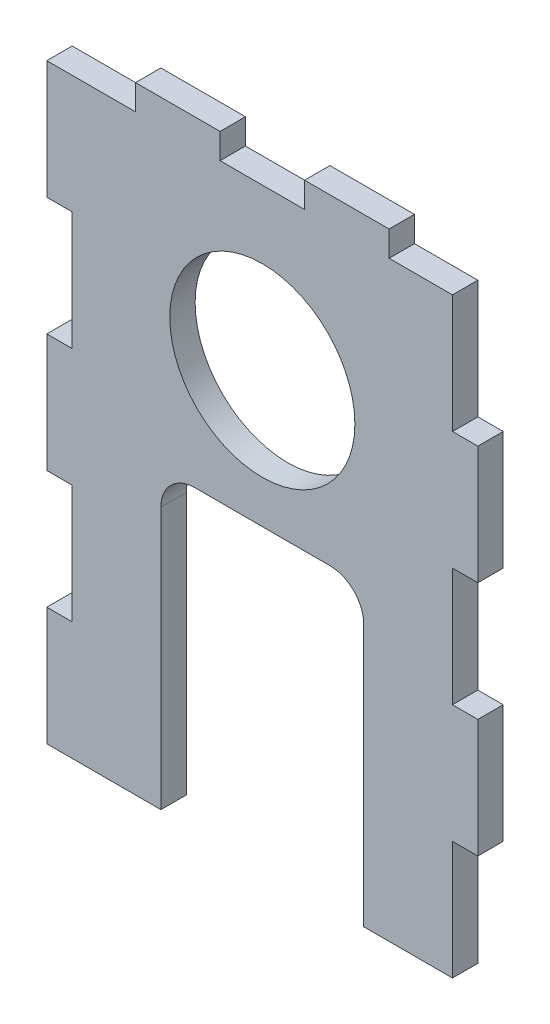
SolidWorks part; units mm, degrees
ref_plane "Front Plane" through (0, 0, 0) normal (0, 0, 1) x (1, 0, 0)
ref_plane "Top Plane" through (0, 0, 0) normal (0, 1, 0) x (1, 0, 0)
ref_plane "Right Plane" through (0, 0, 0) normal (1, 0, 0) x (0, 0, -1)
sketch "Sketch1" plane through (0, 0, 0) normal (0, 0, 1) x (1, 0, 0)
  line L1 (-22.5, -35) -> (22.5, -35)
  line L2 (-22.5, -35) -> (-22.5, 35)
  line L3 (-22.5, 35) -> (22.5, 35)
  line L4 (22.5, -35) -> (22.5, 35)
  line L5 (-22.5, -35) -> (22.5, 35) construction
  line L6 (-22.5, 35) -> (22.5, -35) construction
  point P0 (0, 0)
  dimension "D1" = 70
  dimension "D2" = 45
extrude "Boss-Extrude1" add sketch "Sketch1" along normal blind 3 contours L2 L3 L4 L1
sketch "Sketch2" plane through (0, 0, 3) normal (0, 0, 1) x (1, 0, 0)
  line L0 (-22.5, -35) -> (22.5, -35) construction
  line L1 (-12, 0) -> (12, 0)
  line L2 (-12, 0) -> (-12, -35)
  line L3 (-12, -35) -> (12, -35)
  line L4 (12, 0) -> (12, -35)
  line L5 (-12, 0) -> (12, -35) construction
  line L6 (-12, -35) -> (12, 0) construction
  circle A0 centre (0, 16) radius 10.95
  point P2 (0, -17.5)
  dimension "D1" = 21.9
  dimension "D2" = 16
  dimension "D3" = 24
  dimension "D4" = 35
extrude "Cut-Extrude1" cut sketch "Sketch2" against normal through all
fillet "Fillet1" radius 4 2 edges at (12, 0, 1.5) (-12, 0, 1.5)
sketch "Sketch4" plane through (0, 0, 3) normal (0, 0, 1) x (1, 0, 0)
  line L0 (0, 35) -> (0, 41.52) construction
  line L1 (-15, 35) -> (-5, 35)
  line L2 (-15, 35) -> (-15, 38)
  line L3 (-15, 38) -> (-5, 38)
  line L4 (-5, 35) -> (-5, 38)
  line L5 (-22.5, 35) -> (22.5, 35) construction
  line L6 (5, 35) -> (5, 38)
  line L7 (15, 38) -> (5, 38)
  line L8 (15, 35) -> (15, 38)
  line L9 (15, 35) -> (5, 35)
  dimension "D1" = 3
  dimension "D2" = 10
  dimension "D3" = 10
extrude "Boss-Extrude3" add sketch "Sketch4" against normal up to surface (3 mm away) up to face at (0, -7.6343, 0)
sketch "Sketch3" plane through (0, 0, 0) normal (0, 0, -1) x (-1, 0, 0)
  line L0 (22.5, 7) -> (22.5, -7)
  line L1 (22.5, 35) -> (25.5, 35)
  line L2 (22.5, 35) -> (22.5, 21)
  line L3 (22.5, 21) -> (25.5, 21)
  line L4 (25.5, 35) -> (25.5, 21)
  line L5 (22.5, 7) -> (25.5, 7)
  line L6 (25.5, 7) -> (25.5, -7)
  line L7 (22.5, -7) -> (25.5, -7)
  line L8 (22.5, -21) -> (22.5, -35)
  line L9 (22.5, -21) -> (25.5, -21)
  line L10 (25.5, -21) -> (25.5, -35)
  line L11 (22.5, -35) -> (25.5, -35)
  line L12 (22.5, -35) -> (22.5, 35) construction
  line L13 (-22.5, -35) -> (-22.5, 35) construction
  line L14 (-22.5, 21) -> (-25.5, 21)
  line L15 (-22.5, 21) -> (-22.5, 7)
  line L16 (-22.5, 7) -> (-25.5, 7)
  line L17 (-25.5, 21) -> (-25.5, 7)
  line L18 (22.5, -35) -> (12, -35) construction
  line L19 (-22.5, -7) -> (-25.5, -7)
  line L20 (-22.5, -7) -> (-22.5, -21)
  line L21 (-22.5, -21) -> (-25.5, -21)
  line L22 (-25.5, -7) -> (-25.5, -21)
  dimension "D1" = 3
  dimension "D2" = 14
  dimension "D3" = 3
extrude "Boss-Extrude2" add sketch "Sketch3" against normal up to surface (3 mm away) up to face at (-0.6944, 11.9809, 3)
equation "\"pulley_pitch_diam\"= 12.73mm"
equation "\"pulley_total_width\"= 16mm"
equation "\"belt_width\"= 6mm"
equation "\"material_thickness\"= 3mm"
equation "\"D1@Boss-Extrude1\"=\"material_thickness\""
equation "\"shaft_diam\"= 8mm"
equation "\"D1@Sketch2\"=\"bearing_od\" - 0.1mm"
equation "\"pulley_total_diam\"= 16mm"
equation "\"D2@Sketch2\"=\"pulley_total_diam\" "
equation "\"D3@Sketch2\"=\"pulley_total_width\" * 1.5"
equation "\"D1@Sketch3\"=\"material_thickness\""
equation "\"bearing_od\"= 22mm"
equation "\"bearing_thickness\"= 7mm"
equation "\"D1@Sketch4\"=\"material_thickness\""
